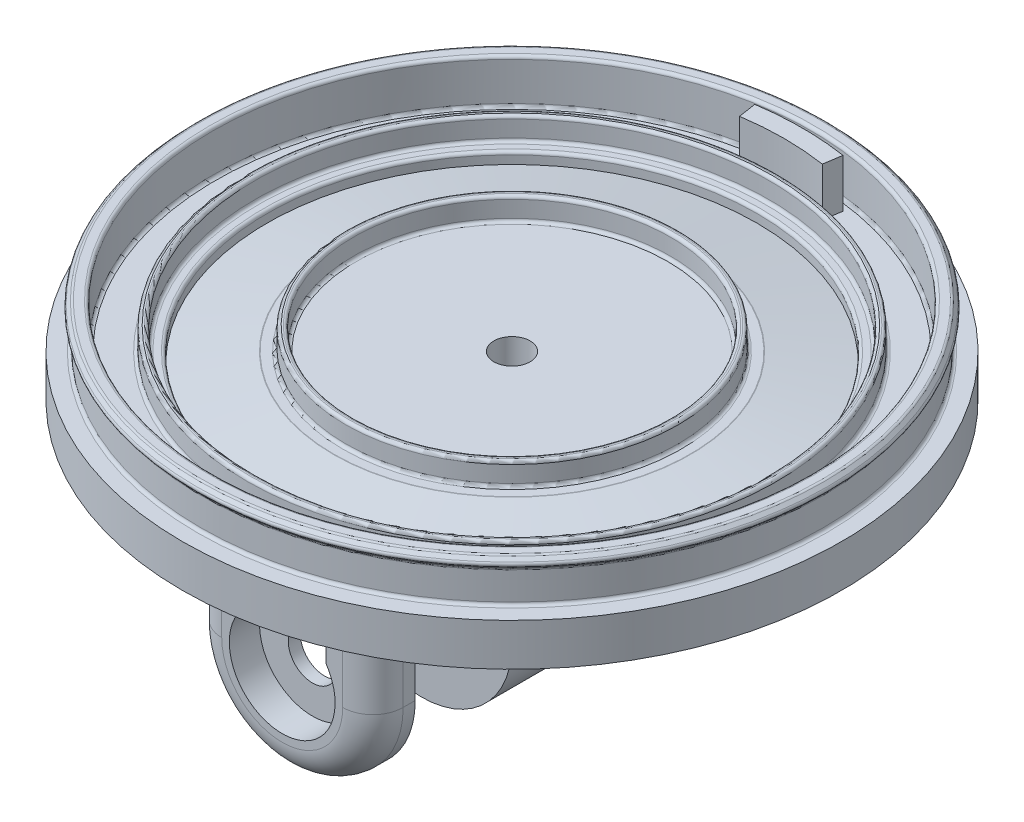
SolidWorks part; units mm, degrees
material "PLA"
ref_plane "Front Plane" through (0, 0, 0) normal (0, 0, 1) x (1, 0, 0)
ref_plane "Top Plane" through (0, 0, 0) normal (0, 1, 0) x (1, 0, 0)
ref_plane "Right Plane" through (0, 0, 0) normal (1, 0, 0) x (0, 0, -1)
sketch "Sketch2" plane through (0, 0, 0) normal (0, 1, 0) x (1, 0, 0)
  circle A0 centre (0, 0) radius 54.5
  dimension "D1" = 109
extrude "Boss-Extrude1" add sketch "Sketch2" along normal blind 7
sketch "Sketch3" plane through (0, 0, 0) normal (0, 0, 1) x (1, 0, 0)
  line L0 (0, 0) -> (0, 7) construction
  line L1 (54.5, 7) -> (-54.5, 7) construction
  line L2 (0, 7) -> (-29.5, 7) construction
  line L3 (-29.5, 7) -> (-40.5, 7)
  line L4 (-40.5, 7) -> (-40.5, 5.127)
  line L5 (-40.5, 5.127) -> (-29.5, 7)
  dimension "D1" = 29.5
  dimension "D2" = 11
  dimension "D3" = 1.873
revolve "Cut-Revolve1" cut sketch "Sketch3" angle 360 about L0
sketch "Sketch4" plane through (0, 7, 0) normal (0, 1, 0) x (1, 0, 0)
  circle A0 centre (0, 0) radius 43.75
  circle A1 centre (0, 0) radius 42.5
  circle A2 centre (0, 0) radius 27.5
  circle A3 centre (0, 0) radius 26.25
  dimension "D1" = 87.5
  dimension "D2" = 85
  dimension "D3" = 55
  dimension "D4" = 52.5
extrude "Boss-Extrude2" add sketch "Sketch4" along normal blind 3.723 contours A0 A1 | A2 A3 region at (-42.5126, 7, 0) region at (-26.7222, 7, 0)
fillet "Fillet1" radius 0.5 10 edges at (0, 7, 26.25) (0, 7, -29.5) (0, 7, -40.5) (0, 10.723, 43.75) (0, 7, 42.5) (0, 10.723, 42.5) (0, 7, 27.5) (0, 10.723, 27.5) (0, 10.723, 26.25) (0, 7, 43.75)
sketch "Sketch5" plane through (0, 0, 0) normal (0, 0, 1) x (1, 0, 0)
  line L0 (0, 7) -> (-49.5, 7) construction
  line L1 (54.5, 7) -> (-54.5, 7) construction
  line L2 (0, 7) -> (0, 24.3916) construction
  line L3 (0, -55) -> (0, 55) construction
  line L4 (-49.5, 7) -> (-51.5, 7)
  line L5 (-51.5, 7) -> (-51.5, 12.323)
  line L6 (-51.5, 12.323) -> (-52.5, 13.323)
  line L7 (-52.5, 13.323) -> (-51.5, 14.323)
  line L8 (-51.5, 14.323) -> (-49.5, 14.323)
  line L9 (-49.5, 14.323) -> (-49.5, 7)
  dimension "D1" = 7.323
  dimension "D2" = 1
  dimension "D3" = 1
  dimension "D4" = 2
  dimension "D5" = 2
  dimension "D6" = 49.5
revolve "Revolve1" add sketch "Sketch5" angle 360 about L2
fillet "Fillet2" radius 0.5 6 edges at (51.5, 7, 0) (49.5, 7, 0) (49.5, 14.323, 0) (51.5, 14.323, 0) (51.5, 12.323, 0) (52.5, 13.323, 0)
sketch "Sketch6" plane through (0, 7, 0) normal (0, 1, 0) x (1, 0, 0)
  circle A0 centre (0, 0) radius 3
  dimension "D1" = 6
extrude "Cut-Extrude1" cut sketch "Sketch6" against normal blind 6
sketch "Sketch7" plane through (0, 0, 0) normal (0, 0, 1) x (1, 0, 0)
  line L0 (-54.5, 0) -> (54.5, 0) construction
  line L1 (-15, 0) -> (15, 0)
  line L2 (-15, 0) -> (-15, -20)
  line L3 (-15, -20) -> (15, -20)
  line L4 (15, 0) -> (15, -20)
  line L5 (-15, -20) -> (-11.025, -20)
  line L6 (11.025, -20) -> (15, -20)
  circle A0 centre (0, -20) radius 15
  circle A1 centre (0, -20) radius 11.025
  arc A2 (11.025, -20) -> (-11.025, -20) centre (0, -20) ccw
  circle A3 centre (0, -20) radius 4
  point P8 (0, 0)
  dimension "D1" = 30
  dimension "D3" = 22.05
  dimension "D4" = 8
  dimension "D2" = 20
extrude "Boss-Extrude3" add sketch "Sketch7" along normal blind 15 and the other way blind 15 contours A0 L4 L1 L2 | A1 L3 A0 | A1 L3 A0 | L3 A1 | L3 A1 region at (0, -4.7914, 0) region at (0, -5.3354, 0) region at (-13.0125, -20.3354, 0) region at (0, -14.8689, 0) region at (0, -25.1311, 0)
sketch "Sketch10" plane through (0, 0, 0) normal (0, 0, 1) x (1, 0, 0)
  line L0 (-54.5, 0) -> (54.5, 0) construction
  line L1 (20.9531, 0) -> (-17.5201, 0)
  line L2 (20.9531, 0) -> (20.9531, -42.1824)
  line L3 (20.9531, -42.1824) -> (-17.5201, -42.1824)
  line L4 (-17.5201, 0) -> (-17.5201, -42.1824)
extrude "Cut-Extrude4" cut sketch "Sketch10" against normal blind 5 and the other way blind 5
sketch "Sketch11" plane through (0, 0, 15) normal (0, 0, 1) x (1, 0, 0)
  line L0 (15, 0) -> (15, -20)
  line L1 (59.95, 0) -> (-59.95, 0) construction
  line L2 (15, 0) -> (15, -20) construction
  line L3 (-15, -20) -> (-15, 0)
  line L4 (-15, 0) -> (-15, -20) construction
  line L5 (-15, 0) -> (15, 0)
  arc A0 (15, -20) -> (-15, -20) centre (0, -20) cw
  circle A1 centre (0, -20) radius 3.5
  circle M5 centre (0, -20) radius 4
  arc M6 (-15, -20) -> (15, -20) centre (0, -20) ccw
  line M7 (15, -20) -> (15, 0)
  line M8 (15, 0) -> (-15, 0)
  line M9 (-15, 0) -> (-15, -20)
  dimension "D1" = 7
extrude "Boss-Extrude4" add sketch "Sketch11" along normal blind 2 from offset 16 contours M9 M6 M7 M8 M5 region at (0, -15.8479, 15)
sketch "Sketch12" plane through (0, 0, 33) normal (0, 0, 1) x (1, 0, 0)
  line L0 (-7.25, 0) -> (-7.25, -15.101)
  line L1 (59.95, 0) -> (-59.95, 0) construction
  line L2 (7.25, 0) -> (7.25, -15.101)
  line L3 (0, -27.1277) -> (0, 27.1277) construction
  line L4 (-7.25, 0) -> (7.25, 0)
  line L5 (-7.25, 0) -> (-15, 0)
  line L6 (-15, 0) -> (-15, -20) construction
  line L7 (7.25, 0) -> (15, 0)
  line L8 (15, -20) -> (15, 0) construction
  line L9 (15, 0) -> (15, -20)
  circle A0 centre (0, -20) radius 8.75
  arc A1 (15, -20) -> (-15, -20) centre (0, -20) cw
  arc A2 (-15, -20) -> (15, -20) centre (0, -20) ccw construction
  line M4 (-15, 0) -> (-15, -20)
  arc M5 (-15, -20) -> (15, -20) centre (0, -20) ccw
  line M6 (15, -20) -> (15, 0)
  line M7 (15, 0) -> (-15, 0)
  dimension "D1" = 17.5
  dimension "D2" = 14.5
  dimension "D3" = 7.25
extrude "Boss-Extrude5" add sketch "Sketch12" along normal blind 5 contours A0 L0 L2 M7 M4 M5 M6 region at (-7.711, -7.5505, 33)
fillet "Fillet3" radius 5 3 edges at (11.125, 0, 38) (-11.125, 0, 38) (-15, -10, 38)
sketch "Sketch13" plane through (0, 7, 0) normal (0, 1, 0) x (1, 0, 0)
  line L0 (7.3019, 47.4414) -> (6.8456, 44.4763)
  line L1 (-7.3019, 47.4414) -> (-6.8456, 44.4763)
  line L2 (-6.8456, 44.4763) -> (0, 0) construction
  line L3 (0, 0) -> (6.8456, 44.4763) construction
  line L4 (0, -27.1277) -> (0, 27.1277) construction
  arc A0 (6.8456, 44.4763) -> (-6.8456, 44.4763) centre (0, 0) ccw
  arc A1 (7.3019, 47.4414) -> (-7.3019, 47.4414) centre (0, 0) ccw
  point P6 (-34.8396, 33.0182)
  point P7 (0, 48)
  dimension "D2" = 45
  dimension "D4" = 48
  dimension "D1" = 17.5
  dimension "D3" = 17.5
extrude "Boss-Extrude6" add sketch "Sketch13" along normal blind 8
